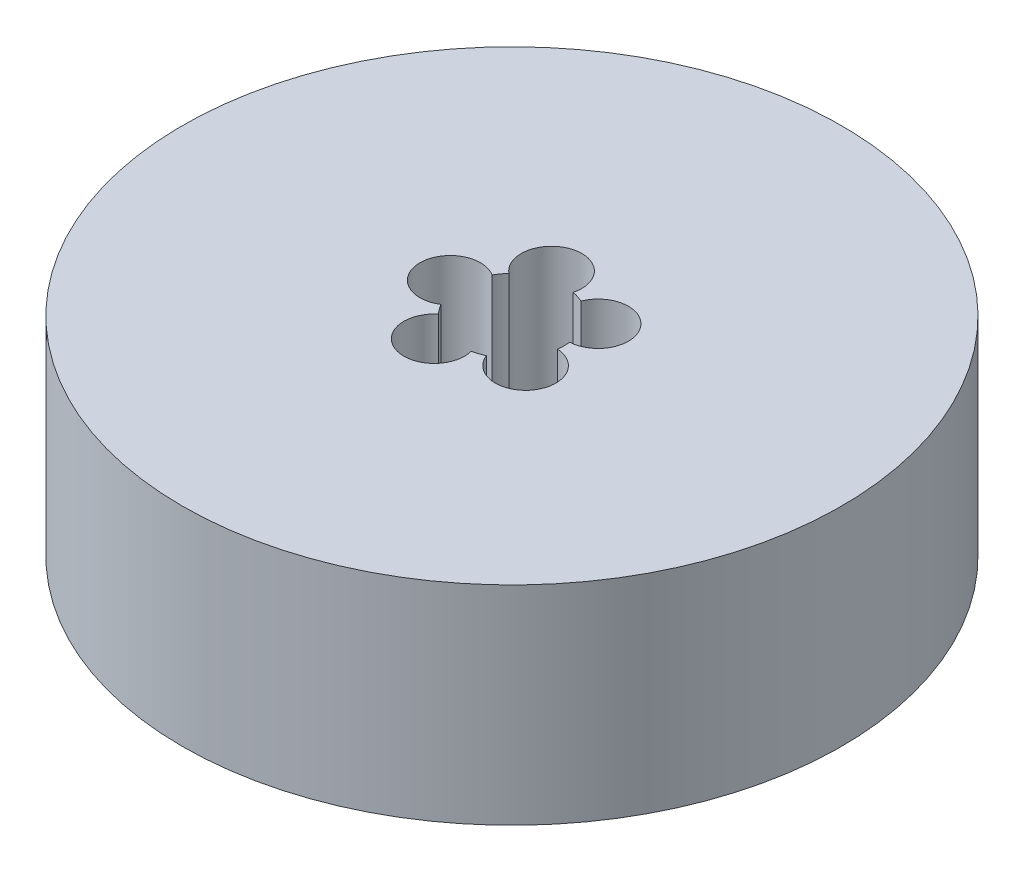
SolidWorks part; units mm, degrees
ref_plane "Front Plane" through (0, 0, 0) normal (0, 0, 1) x (1, 0, 0)
ref_plane "Top Plane" through (0, 0, 0) normal (0, 1, 0) x (1, 0, 0)
ref_plane "Right Plane" through (0, 0, 0) normal (1, 0, 0) x (0, 0, -1)
sketch "Sketch1" plane through (0, 0, 0) normal (0, 1, 0) x (1, 0, 0)
  circle A0 centre (0, 0) radius 47.5
  dimension "FLANGE_OD" = 95
extrude "Boss-Extrude1" add sketch "Sketch1" along normal blind 30
sketch "Sketch2" plane through (0, 0, 0) normal (0, 1, 0) x (1, 0, 0)
  circle A0 centre (0, 0) radius 7.5
  dimension "BORE_D" = 15
extrude "Cut-Extrude1" cut sketch "Sketch2" along normal through all
sketch "Sketch3" plane through (0, 30, 0) normal (0, 1, 0) x (1, 0, 0)
  circle A0 centre (0, 0) radius 8.8924 construction
  circle A1 centre (-8.8924, 0) radius 4.3689
  dimension "BOLT_D" = 8.7378
  dimension "BOLT_PCD" = 17.7848
extrude "Cut-Extrude2" cut sketch "Sketch3" against normal blind 26.8137
pattern_circular "CirPattern1" count 5 over 360 about axis through (0, 0, 0) along (0, 1, 0) of "Cut-Extrude2"
